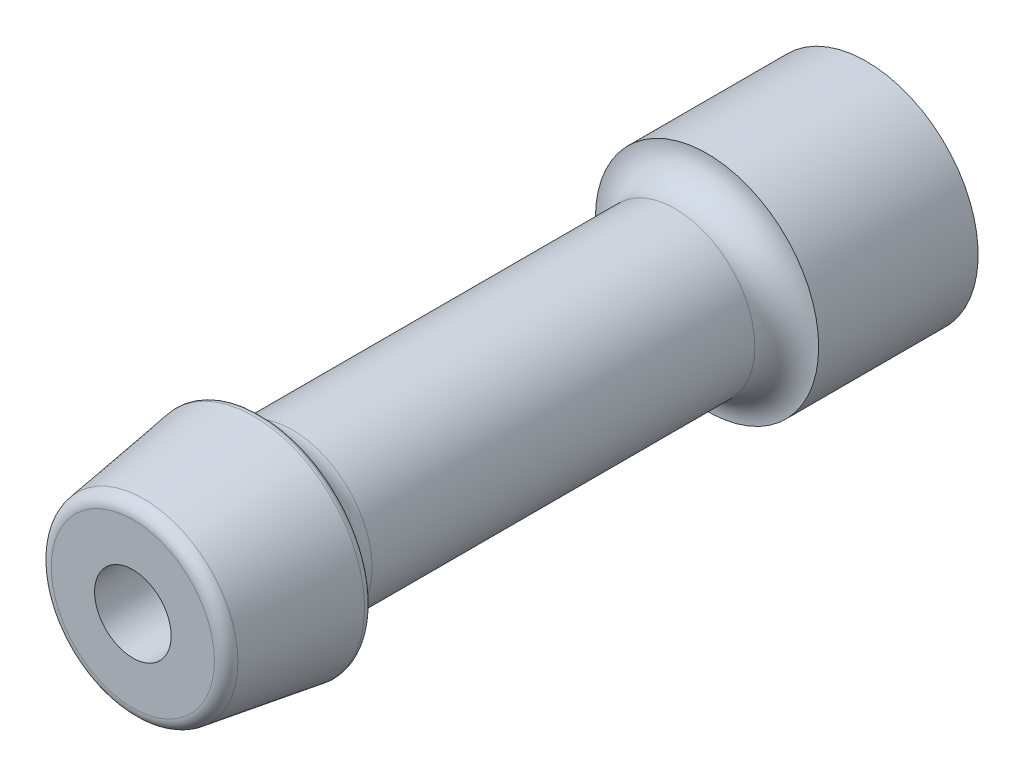
SolidWorks part; units mm, degrees
material "Custom Plastic"
ref_plane "X-Y Datum" through (0, 0, 0) normal (0, 0, 1) x (1, 0, 0)
ref_plane "X-Z Datum" through (0, 0, 0) normal (0, 1, 0) x (1, 0, 0)
ref_plane "Y-Z Datum" through (0, 0, 0) normal (1, 0, 0) x (0, 0, -1)
sketch "Sketch1" plane through (0, 0, 0) normal (0, 0, 1) x (1, 0, 0)
  circle A0 centre (0, 0) radius 4.445
  dimension "D1" = 8.89
extrude "Boss-Extrude1" add sketch "Sketch1" along normal blind 29.21
sketch3d "3DSketch1"
  line L0 (0, 0, 29.21) -> (0, 0, 0)
  line L1 (0, 0, 29.21) -> (0, 0, 0) construction
sketch "Sketch2" plane through (0, 0, 29.21) normal (0, 0, 1) x (1, 0, 0)
  circle A0 centre (0, 0) radius 1.524
  dimension "D1" = 3.048
sweep "Cut-Sweep1" cut profiles "Sketch2" path "3DSketch1"
sketch "Sketch3" plane through (0, 0, 29.21) normal (0, 0, 1) x (1, 0, 0)
  circle A0 centre (0, 0) radius 3.175
  circle A1 centre (0, 0) radius 6.35
  dimension "D1" = 12.7
  dimension "D2" = 6.35
extrude "Cut-Extrude1" cut sketch "Sketch3" against normal blind 17.78 from offset 5.08 offset against normal yes
fillet "Fillet1" radius 1.27 1 edges at (3.175, 0, 6.35)
fillet "Fillet2" radius 1.27 1 edges at (3.175, 0, 24.13)
chamfer "Chamfer1" distance 5.08 angle 8.5 1 edges at (4.445, 0, 29.21) first distance on face at (4.445, 0, 24.13)
fillet "Fillet3" radius 0.254 1 edges at (4.445, 0, 24.13)
fillet "Fillet4" radius 0.508 1 edges at (3.6858, 0, 29.21)
